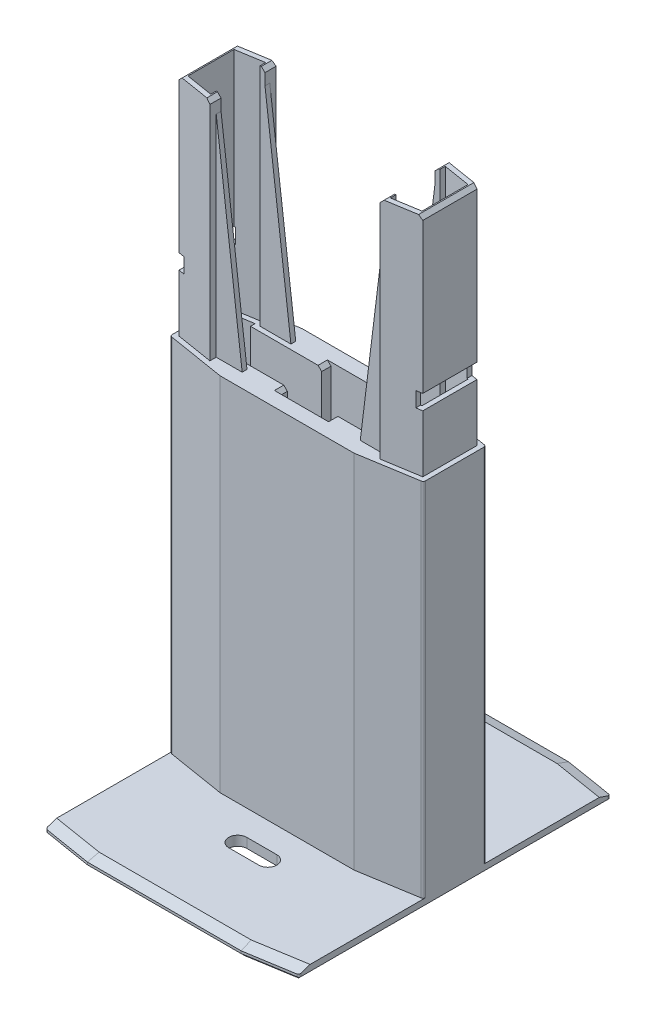
SolidWorks part; units mm, degrees
ref_plane "Front" through (0, 0, 0) normal (0, 0, 1) x (1, 0, 0)
ref_plane "Top" through (0, 0, 0) normal (0, 1, 0) x (1, 0, 0)
ref_plane "Right" through (0, 0, 0) normal (1, 0, 0) x (0, 0, -1)
sketch "Sketch1" plane through (0, 0, 0) normal (0, 1, 0) x (1, 0, 0)
  line L0 (0, -738.6263) -> (0, 36192.6906) construction
  line L1 (-738.6263, 0) -> (36192.6906, 0) construction
  line L2 (-40.5, -9) -> (-40.5, 9)
  line L3 (-40.5, 9) -> (-28.25, 11)
  line L4 (-28.25, 11) -> (-28.25, 8.9)
  line L5 (-28.25, 8.9) -> (-11, 8.9)
  line L6 (-11, 8.9) -> (-11, 12)
  line L7 (-11, 12) -> (11, 12)
  line L8 (-11, -12) -> (11, -12)
  line L9 (-11, -8.9) -> (-11, -12)
  line L10 (-28.25, -8.9) -> (-11, -8.9)
  line L11 (-28.25, -11) -> (-28.25, -8.9)
  line L12 (-40.5, -9) -> (-28.25, -11)
  line L13 (40.5, -9) -> (28.25, -11)
  line L14 (28.25, -11) -> (28.25, -8.9)
  line L15 (28.25, -8.9) -> (11, -8.9)
  line L16 (11, -8.9) -> (11, -12)
  line L17 (11, 8.9) -> (11, 12)
  line L18 (28.25, 8.9) -> (11, 8.9)
  line L19 (28.25, 11) -> (28.25, 8.9)
  line L20 (40.5, 9) -> (28.25, 11)
  line L21 (40.5, -9) -> (40.5, 9)
  line L42 (-22.2548, 13.6) -> (22.2548, 13.6)
  line L43 (-42.1, -10.36) -> (-42.1, 10.36)
  line L44 (-42.1, 10.36) -> (-22.2548, 13.6)
  line L45 (42.1, 10.36) -> (22.2548, 13.6)
  line L46 (42.1, -10.36) -> (42.1, 10.36)
  line L47 (42.1, -10.36) -> (22.2548, -13.6)
  line L48 (-22.2548, -13.6) -> (22.2548, -13.6)
  line L49 (-42.1, -10.36) -> (-22.2548, -13.6)
  line L50 (-1066.7659, 42.5) -> (48933.2341, 42.5) construction
  line L51 (-1082.2929, -42.5) -> (48917.7071, -42.5) construction
  line L52 (-38.9, 7.64) -> (-29.85, 9.1176)
  line L53 (-29.85, 9.1176) -> (-29.85, 7.3)
  line L54 (-29.85, 7.3) -> (-9.4, 7.3)
  line L55 (-9.4, 7.3) -> (-9.4, 10.4)
  line L56 (-9.4, 10.4) -> (9.4, 10.4)
  line L57 (9.4, 7.3) -> (9.4, 10.4)
  line L58 (29.85, 7.3) -> (9.4, 7.3)
  line L59 (29.85, 9.1176) -> (29.85, 7.3)
  line L60 (38.9, 7.64) -> (29.85, 9.1176)
  line L61 (38.9, -7.64) -> (38.9, 7.64)
  line L62 (38.9, -7.64) -> (29.85, -9.1176)
  line L63 (29.85, -9.1176) -> (29.85, -7.3)
  line L64 (29.85, -7.3) -> (9.4, -7.3)
  line L65 (9.4, -7.3) -> (9.4, -10.4)
  line L66 (-9.4, -10.4) -> (9.4, -10.4)
  line L67 (-9.4, -7.3) -> (-9.4, -10.4)
  line L68 (-29.85, -7.3) -> (-9.4, -7.3)
  line L69 (-29.85, -9.1176) -> (-29.85, -7.3)
  line L70 (-38.9, -7.64) -> (-29.85, -9.1176)
  line L71 (-38.9, -7.64) -> (-38.9, 7.64)
  line L72 (-31.45, -5.7) -> (-7.8, -5.7)
  line L73 (-7.8, -5.7) -> (-7.8, -8.8)
  line L74 (-7.8, -8.8) -> (7.8, -8.8)
  line L75 (7.8, -5.7) -> (7.8, -8.8)
  line L76 (31.45, -5.7) -> (7.8, -5.7)
  line L77 (31.45, -7.2352) -> (31.45, -5.7)
  line L78 (37.3, -6.2801) -> (31.45, -7.2352)
  line L79 (37.3, -6.2801) -> (37.3, 6.2801)
  line L80 (37.3, 6.2801) -> (31.45, 7.2352)
  line L81 (31.45, 7.2352) -> (31.45, 5.7)
  line L82 (31.45, 5.7) -> (7.8, 5.7)
  line L83 (7.8, 5.7) -> (7.8, 8.8)
  line L84 (-7.8, 8.8) -> (7.8, 8.8)
  line L85 (-7.8, 5.7) -> (-7.8, 8.8)
  line L86 (-31.45, 5.7) -> (-7.8, 5.7)
  line L87 (-31.45, 7.2352) -> (-31.45, 5.7)
  line L88 (-37.3, 6.2801) -> (-31.45, 7.2352)
  line L89 (-37.3, -6.2801) -> (-37.3, 6.2801)
  line L90 (-37.3, -6.2801) -> (-31.45, -7.2352)
  line L91 (-31.45, -7.2352) -> (-31.45, -5.7)
  point P17 (-40.5, 0)
  point P22 (0, -12)
  point P23 (0, 12)
  point P27 (40.5, 0)
  point P54 (0, 13.6)
  point P57 (42.1, 0)
  point P60 (-42.1, 0)
  dimension "D1" = 81
  dimension "D2" = 24
  dimension "D4" = 18
  dimension "D5" = 17.25
  dimension "D6" = 12.25
  dimension "D7" = 3.1
  dimension "D9" = 85
  dimension "D10" = 42.5
  dimension "D11" = 1.6
  dimension "D12" = 1.6
  dimension "D13" = 1.6
  dimension "D3" = 22
  dimension "D8" = 1.6
  dimension "D15" = 1.6
extrude "Boss-Extrude1" add sketch "Sketch1" along normal blind 123.2 contours L49 L48 L47 L46 L45 L42 L44 L43
extrude "Boss-Extrude2" add sketch "Sketch1<3>" along normal blind 75 from surface contours L13 L21 L20 L19 L18 L17 L7 L6 L5 L4 L3 L2 L12 L11 L10 L9 L8 L16 L15 L14 L70 L71 L52 L53 L54 L55 L56 L57 L58 L59 L60 L61 L62 L63 L64 L65 L66 L67 L68 L69 region at (-39.6552, 0, 0) starting at face at (0, 123.2, 0)
sketch "Sketch1<3>" plane through (0, 0, 0) normal (0, 1, 0) x (1, 0, 0) same geometry as "Sketch1"
sketch "Sketch2" plane through (0, 0, 0) normal (0, 0, 1) x (1, 0, 0)
  line L0 (0, -1007.7521) -> (0, 48992.2479) construction
  line L2 (-40.5, 147.2) -> (-38.5, 147.2)
  line L3 (-40.5, 147.2) -> (-40.5, 142.2)
  line L4 (-40.5, 142.2) -> (-38.5, 142.2)
  line L5 (-38.5, 147.2) -> (-38.5, 142.2)
  line L6 (-40.5, 147.2) -> (-38.5, 142.2) construction
  line L7 (-40.5, 142.2) -> (-38.5, 147.2) construction
  line L8 (-40.5, 198.2) -> (-40.5, 123.2) construction
  line L9 (40.5, 142.2) -> (38.5, 147.2) construction
  line L10 (40.5, 147.2) -> (38.5, 142.2) construction
  line L11 (38.5, 147.2) -> (38.5, 142.2)
  line L12 (40.5, 142.2) -> (38.5, 142.2)
  line L13 (40.5, 147.2) -> (40.5, 142.2)
  line L14 (40.5, 147.2) -> (38.5, 147.2)
  line L16 (-40.5, 198.2) -> (-28.25, 198.2) construction
  point P1 (-39.5, 144.7)
  point P16 (39.5, 144.7)
  dimension "D1" = 2
  dimension "D2" = 5
  dimension "D3" = 51
extrude "Cut-Extrude1" cut sketch "Sketch2" against normal through all both and the other way through all
sketch "Sketch3" plane through (0, 0, 0) normal (0, 0, 1) x (1, 0, 0)
  line L0 (0, -1021.8671) -> (0, 48978.1329) construction
  line L2 (-11, 198.2) -> (11, 198.2) construction
  line L3 (-28.25, 193.2) -> (-19.625, 123.2)
  line L4 (-19.625, 123.2) -> (19.625, 123.2)
  line L5 (28.25, 193.2) -> (19.625, 123.2)
  line L6 (-19.625, -996.8) -> (-19.625, 49003.2) construction
  line L7 (-28.25, 123.2) -> (-11, 123.2) construction
  line L8 (19.625, -996.8) -> (19.625, 49003.2) construction
  line L9 (28.25, 123.2) -> (11, 123.2) construction
  line L10 (-42.1, 123.2) -> (-22.2548, 123.2) construction
  line L13 (-28.25, 198.2) -> (-28.25, 123.2) construction
  line L14 (-28.25, 193.2) -> (-28.25, 198.2)
  line L15 (-28.25, 198.2) -> (28.25, 198.2)
  line L16 (28.25, 198.2) -> (28.25, 193.2)
  point P12 (0, 3.2)
  point P13 (0, 198.2)
  point P18 (-19.625, 123.2)
  point P23 (19.625, 123.2)
  dimension "D1" = 5
extrude "Cut-Extrude2" cut sketch "Sketch3" against normal through all both and the other way through all
sketch "Sketch4" plane through (0, 0, 0) normal (0, 1, 0) x (1, 0, 0)
  line L9 (0, -1000) -> (0, 49000) construction
  line L12 (-1000, 0) -> (49000, 0) construction
  line L39 (23.2928, 26.4) -> (44.1625, 22.9927)
  line L40 (-23.2928, 26.4) -> (23.2928, 26.4)
  line L41 (-44.1625, 22.9927) -> (-23.2928, 26.4)
  line L42 (23.2928, 26.4) -> (42.1, 23.3294)
  line L43 (-23.2928, 26.4) -> (23.2928, 26.4)
  line L44 (-42.1, 23.3294) -> (-23.2928, 26.4)
  line L45 (-42.1, -10.36) -> (-42.1, 10.36) construction
  line L46 (42.1, -10.36) -> (42.1, 10.36) construction
  line L47 (-42.1, -23.3294) -> (-42.1, 23.3294)
  line L48 (23.2928, -26.4) -> (44.1625, -22.9927)
  line L49 (-23.2928, -26.4) -> (23.2928, -26.4)
  line L50 (-44.1625, -22.9927) -> (-23.2928, -26.4)
  line L51 (23.2928, -26.4) -> (42.1, -23.3294)
  line L52 (-23.2928, -26.4) -> (23.2928, -26.4)
  line L53 (-42.1, -23.3294) -> (-23.2928, -26.4)
  line L54 (42.1, -23.3294) -> (42.1, 23.3294)
  dimension "D1" = 12.8
  dimension "D2" = 12.8
extrude "Boss-Extrude3" add sketch "Sketch4" along normal blind 3.2
extrude "Cut-Extrude3" cut sketch "Sketch1<4>" against normal through all and the other way through all contours L90 L91 L72 L73 L74 L75 L76 L77 L78 L79 L80 L81 L82 L83 L84 L85 L86 L87 L88 L89
sketch "Sketch1<4>" plane through (0, 0, 0) normal (0, 1, 0) x (1, 0, 0) same geometry as "Sketch1"
sketch "Sketch5" plane through (0, 0, 0) normal (0, 1, 0) x (1, 0, 0)
  line L6 (0, -1000) -> (0, 49000) construction
  line L16 (-1000, 0) -> (49000, 0) construction
  line L17 (-986.3057, 42.5) -> (49013.6943, 42.5) construction
  line L18 (-977.9486, -42.5) -> (49022.0514, -42.5) construction
  line L21 (42.1, 23.3294) -> (23.2928, 26.4) construction
  line L22 (23.2928, 26.4) -> (-23.2928, 26.4) construction
  line L23 (-23.2928, 26.4) -> (-42.1, 23.3294) construction
  line L24 (42.1, 23.3294) -> (23.2928, 26.4)
  line L25 (23.2928, 26.4) -> (-23.2928, 26.4)
  line L26 (-23.2928, 26.4) -> (-42.1, 23.3294)
  line L28 (23.2928, -26.4) -> (42.1, -23.3294) construction
  line L31 (-23.2928, -26.4) -> (23.2928, -26.4) construction
  line L41 (-42.1, -51.7002) -> (-25.5635, -54.4)
  line L42 (-25.5635, -54.4) -> (25.5635, -54.4)
  line L43 (25.5635, -54.4) -> (42.1, -51.7002)
  line L44 (-42.1, -23.3294) -> (-42.1, -51.7002)
  line L45 (42.1, -23.3294) -> (42.1, -51.7002)
  line L46 (-42.1, 23.3294) -> (-42.1, 51.7002)
  line L47 (-42.1, -23.3294) -> (-23.2928, -26.4) construction
  line L48 (23.2928, -26.4) -> (42.1, -23.3294)
  line L49 (42.1, 23.3294) -> (42.1, 51.7002)
  line L62 (25.5635, 54.4) -> (42.1, 51.7002)
  line L63 (-25.5635, 54.4) -> (25.5635, 54.4)
  line L64 (-42.1, 51.7002) -> (-25.5635, 54.4)
  line L65 (-23.2928, -26.4) -> (23.2928, -26.4)
  line L66 (-42.1, -23.3294) -> (-23.2928, -26.4)
  point P5 (-45.5781, -51.0515)
  point P9 (45.5781, -51.0515)
  dimension "D1" = 85
  dimension "D2" = 42.5
  dimension "D3" = 28
  dimension "D4" = 28
  dimension "D5" = 28
extrude "Boss-Extrude4" add sketch "Sketch5" along normal up to surface (3.2 mm away) up to face at (0, 3.2, 18.4223)
sketch "Sketch6" plane through (0, 0, 0) normal (0, 1, 0) x (1, 0, 0)
  line L4 (0, 0) -> (50000, 0) construction
  line L7 (25.5635, 54.4) -> (42.1, 51.7002) construction
  line L8 (-25.5635, 54.4) -> (25.5635, 54.4) construction
  line L24 (-42.1, 51.7002) -> (-25.5635, 54.4) construction
  line L25 (25.5635, 54.4) -> (42.1, 51.7002)
  line L26 (-25.5635, 54.4) -> (25.5635, 54.4)
  line L27 (-42.1, 51.7002) -> (-25.5635, 54.4)
  line L30 (-42.1, -10.36) -> (-42.1, 10.36) construction
  line L31 (42.1, -10.36) -> (42.1, 10.36) construction
  line L32 (-42.1, 48.1002) -> (42.1, 48.1002)
  line L33 (-42.1, 48.1002) -> (-42.1, 51.7002)
  line L34 (42.1, 48.1002) -> (42.1, 51.7002)
  line L35 (42.1, -48.1002) -> (42.1, -51.7002)
  line L36 (-42.1, -48.1002) -> (-42.1, -51.7002)
  line L37 (-42.1, -48.1002) -> (42.1, -48.1002)
  line L38 (-42.1, -51.7002) -> (-25.5635, -54.4)
  line L39 (-25.5635, -54.4) -> (25.5635, -54.4)
  line L40 (25.5635, -54.4) -> (42.1, -51.7002)
  point P2 (-42.1, 40.9)
  point P3 (42.1, 40.9)
  dimension "D1" = 3.6
extrude "Boss-Extrude5" add sketch "Sketch6" along normal up to surface (3.2 mm away) up to face at (0, 3.2, 32.515)
sketch "Sketch7" plane through (0, 0, 0) normal (0, 1, 0) x (0, 0, -1)
  line L0 (25, -5) -> (25, 5) construction
  line L5 (28, -5) -> (28, 5)
  line L6 (22, -5) -> (22, 5)
  line L8 (0, -1000) -> (0, 49000) construction
  line L17 (-25, -5) -> (-25, 5) construction
  line L22 (-28, -5) -> (-28, 5)
  line L23 (-22, -5) -> (-22, 5)
  arc A2 (-28, -5) -> (-22, -5) centre (-25, -5) ccw
  arc A3 (-22, 5) -> (-28, 5) centre (-25, 5) ccw
  arc A4 (28, -5) -> (22, -5) centre (25, -5) cw
  arc A5 (22, 5) -> (28, 5) centre (25, 5) cw
  point P4 (-25, 0)
  point P15 (25, 0)
  dimension "D1" = 25
  dimension "D2" = 3
  dimension "D3" = 10
extrude "Cut-Extrude4" cut sketch "Sketch7" against normal up to surface (-123.2 mm away) contours L5 | L23 A3 L22 A2 | A5 L6 A4 L5 region at (0, 0, -25) region at (0, 0, 25) up to face at (0, 123.2, 0)
chamfer "Chamfer1" distance 1.2 distance2 3.6 6 edges at (33.8317, 3.2, 53.0501) (-33.8317, 3.2, 53.0501) (0, 3.2, 54.4) (-33.8317, 3.2, -53.0501) (0, 3.2, -54.4) (33.8317, 3.2, -53.0501) tangent propagation no first distance on face at (33.8317, 1.6, 53.0501) first distance on face at (-33.8317, 1.6, 53.0501) first distance on face at (0, 1.6, 54.4) first distance on face at (-33.8317, 1.6, -53.0501) first distance on face at (0, 1.6, -54.4) first distance on face at (33.8317, 1.6, -53.0501)
chamfer "Chamfer2" distance 1.2 angle 45 22 edges at (33.8317, 0, 53.0501) (0, 0, 54.4) (-33.8317, 0, 53.0501) (-42.1, 0, 0) (-33.8317, 0, -53.0501) (0, 0, -54.4) (33.8317, 0, -53.0501) (42.1, 0, 0) (40.5, 198.2, 0) (-40.5, 198.2, 0) (28.25, 198.2, -9.15) (28.25, 198.2, 9.15) (-28.25, 198.2, -9.15) (-28.25, 198.2, 9.15) (-7.8, 0, 7.25) (-7.8, 0, -7.25) (7.8, 0, 7.25) (7.8, 0, -7.25) (7.8, 123.2, 7.25) (7.8, 123.2, -7.25) (-7.8, 123.2, -7.25) (-7.8, 123.2, 7.25)
fillet "Fillet1" radius 0.8 8 edges at (42.1, 1.6, 51.7002) (42.1, 1.6, -51.7002) (-42.1, 1.6, -51.7002) (-42.1, 1.6, 51.7002) (42.1, 63.2, -10.36) (42.1, 63.2, 10.36) (-42.1, 63.2, 10.36) (-42.1, 63.2, -10.36)
equation "\"D11@Sketch1\"=\"D8@Sketch1\""
equation "\"D12@Sketch1\"=\"D8@Sketch1\""
equation "\"D13@Sketch1\"=\"D8@Sketch1\""
equation "\"D2@Sketch5\"=\"D1@Sketch5\"/2"
